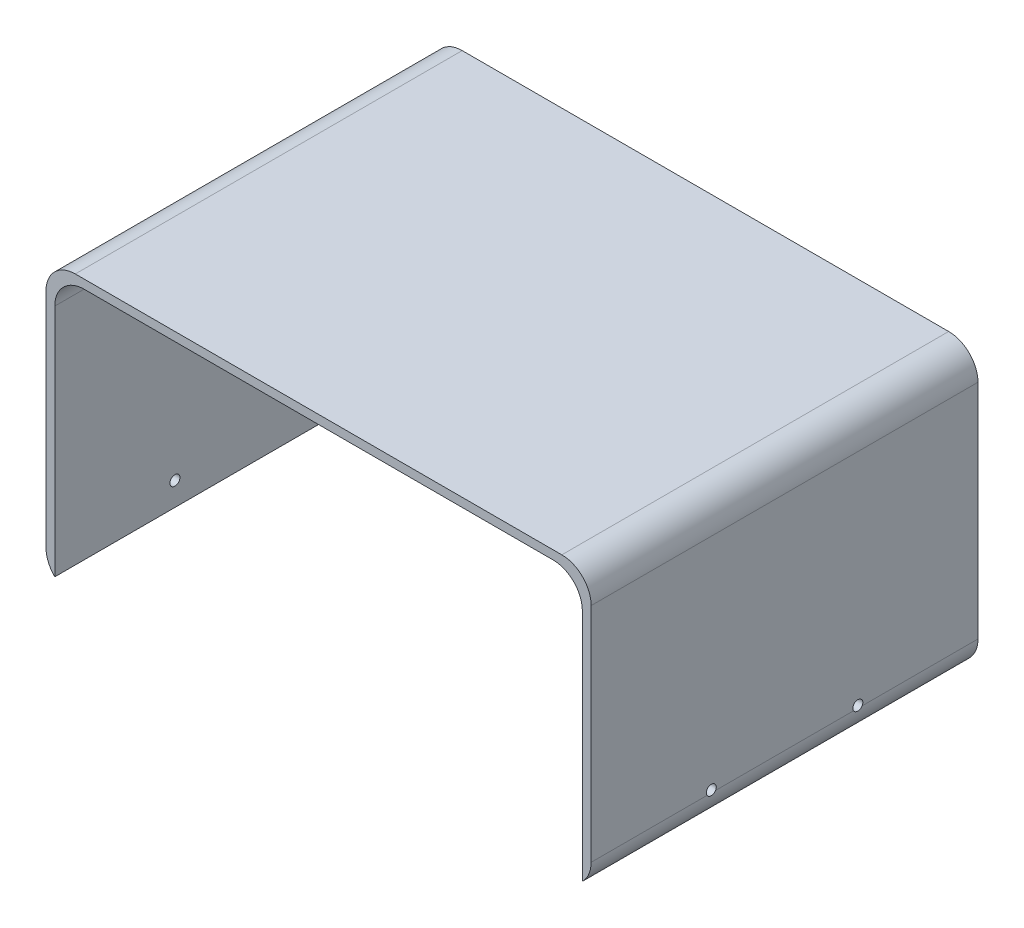
SolidWorks part; units mm, degrees
ref_plane "Front Plane" through (0, 0, 0) normal (0, 0, 1) x (1, 0, 0)
ref_plane "Top Plane" through (0, 0, 0) normal (0, 1, 0) x (1, 0, 0)
ref_plane "Right Plane" through (0, 0, 0) normal (1, 0, 0) x (0, 0, -1)
sketch "Sketch1" plane through (0, 0, 0) normal (1, 0, 0) x (0, 0, -1)
  line L5 (0, 0) -> (132, 0)
  line L6 (0, 0) -> (0, -93)
  line L7 (0, -93) -> (132, -93)
  line L8 (132, 0) -> (132, -93)
  dimension "D1" = 93
  dimension "D2" = 132
extrude "Boss-Extrude1" add sketch "Sketch1" along normal blind 3
sketch "Sketch3" plane through (0, 0, 0) normal (-1, 0, 0) x (0, 0, 1)
  line L0 (0, 0) -> (0, -93) construction
  line L5 (-132, 0) -> (0, 0)
  line L6 (-132, 0) -> (-132, -3)
  line L7 (-132, -3) -> (0, -3)
  line L8 (0, 0) -> (0, -3)
  dimension "D1" = 3
extrude "Boss-Extrude2" add sketch "Sketch3" along normal blind 180
sketch "Sketch4" plane through (0, 0, 0) normal (-1, 0, 0) x (0, 0, 1)
  line L5 (-132, 0) -> (0, 0)
  line L6 (-132, 0) -> (-132, -93)
  line L7 (-132, -93) -> (0, -93)
  line L8 (0, 0) -> (0, -93)
  dimension "D1" = 93
  dimension "D2" = 132
extrude "Boss-Extrude3" add sketch "Sketch4" along normal blind 3 from offset 180
fillet "Fillet1" radius 10 4 edges at (0, -3, -66) (3, 0, -66) (-183, 0, -66) (-180, -3, -66)
fillet "Fillet2" radius 10 2 edges at (3, -93, -66) (-183, -93, -66)
sketch "Sketch5" plane through (0, 0, 0) normal (-1, 0, 0) x (0, 0, 1)
  line L0 (-132, -93) -> (-132, -13) construction
  line L1 (0, -13) -> (0, -93) construction
  line L2 (0, -93) -> (-132, -93) construction
  circle A0 centre (-91, -85) radius 1.7
  circle A1 centre (-41, -85) radius 1.7
  dimension "D1" = 41
  dimension "D5" = 3.4
  dimension "D6" = 3.4
  dimension "D2" = 41
  dimension "D3" = 8
  dimension "D4" = 8
  dimension "D7" = 50
extrude "Cut-Extrude1" cut sketch "Sketch5" against normal through all both and the other way through all
